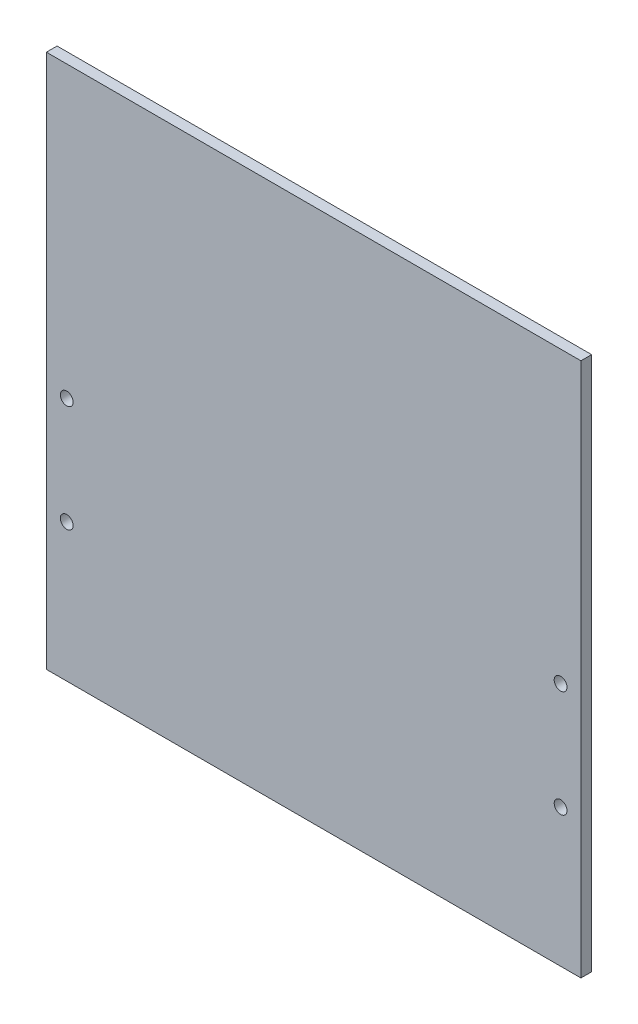
SolidWorks part; units mm, degrees
ref_plane "Front Plane" through (0, 0, 0) normal (0, 0, 1) x (1, 0, 0)
ref_plane "Top Plane" through (0, 0, 0) normal (0, 1, 0) x (1, 0, 0)
ref_plane "Right Plane" through (0, 0, 0) normal (1, 0, 0) x (0, 0, -1)
sketch "Sketch1" plane through (0, 0, 0) normal (0, 0, 1) x (1, 0, 0)
  line L1 (-125, 125) -> (125, 125)
  line L2 (-125, 125) -> (-125, -125)
  line L3 (-125, -125) -> (125, -125)
  line L4 (125, 125) -> (125, -125)
  line L5 (-125, 125) -> (125, -125) construction
  line L6 (-125, -125) -> (125, 125) construction
  circle A2 centre (-115.5, -10.5) radius 3
  circle A3 centre (-115.5, -60.5) radius 3
  circle A4 centre (115.5, -10.5) radius 3
  circle A5 centre (115.5, -60.5) radius 3
  point P0 (0, 0)
  dimension "D3" = 6
  dimension "D1" = 250
  dimension "D2" = 250
extrude "Boss-Extrude1" add sketch "Sketch1" along normal blind 5
